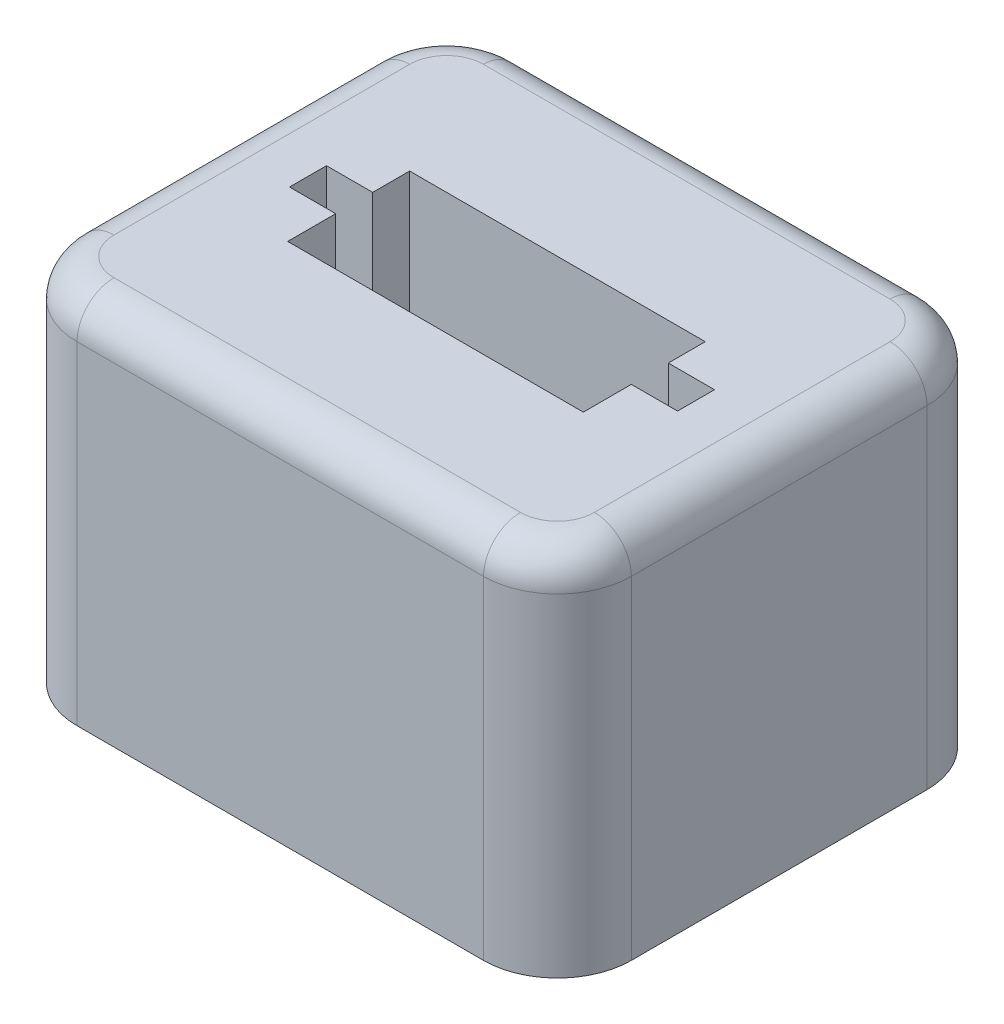
SolidWorks part; units mm, degrees
ref_plane "Спереди" through (0, 0, 0) normal (0, 0, 1) x (1, 0, 0)
ref_plane "Сверху" through (0, 0, 0) normal (0, 1, 0) x (1, 0, 0)
ref_plane "Справа" through (0, 0, 0) normal (1, 0, 0) x (0, 0, -1)
sketch "Эскиз1" plane through (0, 0, 0) normal (0, 1, 0) x (1, 0, 0)
  line L1 (4, 0) -> (26, 0)
  line L2 (0, 4) -> (0, 20)
  line L3 (4, 24) -> (26, 24)
  line L4 (30, 4) -> (30, 20)
  arc A0 (26, 24) -> (30, 20) centre (26, 20) cw
  arc A1 (26, 0) -> (30, 4) centre (26, 4) ccw
  arc A2 (4, 0) -> (0, 4) centre (4, 4) cw
  arc A3 (0, 20) -> (4, 24) centre (4, 20) cw
  point P10 (30, 0)
  point P13 (0, 0)
  point P16 (0, 24)
  dimension "D3" = 4
  dimension "D1" = 30
  dimension "D2" = 24
extrude "Тело" add sketch "Эскиз1" along normal blind 20
fillet "Скругление1" radius 2 8 edges at (15, 20, 0) (28.8284, 20, -1.1716) (1.1716, 20, -1.1716) (0, 20, -12) (1.1716, 20, -22.8284) (15, 20, -24) (28.8284, 20, -22.8284) (30, 20, -12)
sketch "Эскиз6" plane through (0, 0, 0) normal (0, -1, 0) x (1, 0, 0)
  circle A0 centre (4, -4) radius 0.9
  circle A1 centre (26, -4) radius 0.9
  circle A2 centre (26, -20) radius 0.9
  circle A3 centre (4, -20) radius 0.9
  dimension "D1" = 1.8
extrude "Крепеж" cut sketch "Эскиз6" against normal blind 7
sketch "Эскиз3" plane through (0, 20, 0) normal (0, 1, 0) x (1, 0, 0)
  line L1 (7, 11.4) -> (23, 11.4)
  line L2 (7, 11.4) -> (7, 8.4)
  line L3 (7, 8.4) -> (23, 8.4)
  line L4 (23, 11.4) -> (23, 8.4)
  line L5 (4, 0) -> (26, 0) construction
  point P7 (15, 0)
  point P11 (15, 8.4)
  dimension "D1" = 16
  dimension "D2" = 3
  dimension "D3" = 8.4
extrude "Разъем" cut sketch "Эскиз3" against normal up to next
sketch "Эскиз2" plane through (0, 20, 0) normal (0, 1, 0) x (1, 0, 0)
  line L1 (4.5, 13) -> (25.5, 13)
  line L2 (4.5, 13) -> (4.5, 11)
  line L3 (4.5, 11) -> (25.5, 11)
  line L4 (25.5, 13) -> (25.5, 11)
  line L5 (23, 11.4) -> (7, 11.4) construction
  point P4 (15, 11)
  point P6 (0, 0)
  point P7 (0, 0)
  point P11 (15, 11.4)
  dimension "D1" = 2
  dimension "D2" = 21
  dimension "D3" = 0.4
extrude "Плата" cut sketch "Эскиз2" against normal offset from surface (12 mm away) 8 up to face at (15, 0, -9.9)
sketch "Эскиз7" plane through (0, 20, 0) normal (0, 1, 0) x (1, 0, 0)
  line L0 (25.5, 13) -> (4.5, 13) construction
  line L1 (7, 13) -> (23, 13)
  line L2 (7, 13) -> (7, 15)
  line L3 (7, 15) -> (23, 15)
  line L4 (23, 13) -> (23, 15)
  line L5 (7, 11) -> (7, 8.4) construction
  line L6 (23, 8.4) -> (23, 11) construction
  dimension "D1" = 2
extrude "Вырез-Вытянуть1" cut sketch "Эскиз7" against normal offset from surface (8.7 mm away) 3.3 up to face at (15, 8, -11.6)
